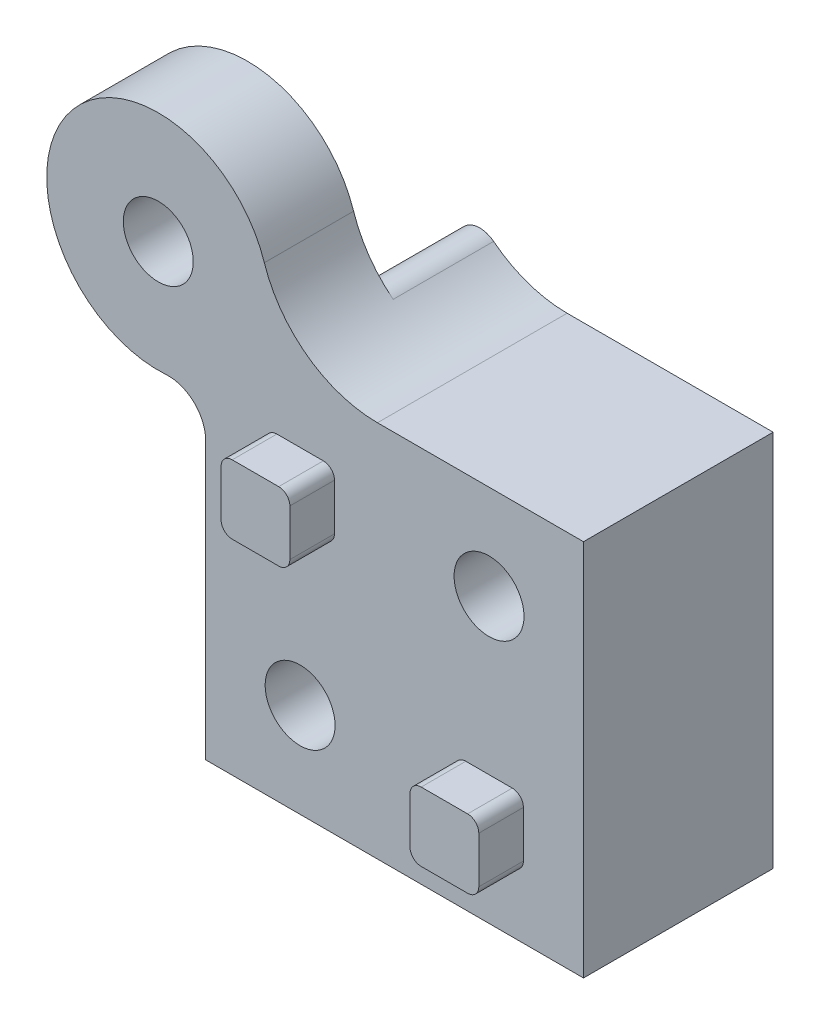
SolidWorks part; units mm, degrees
ref_plane "Front Plane" through (0, 0, 0) normal (0, 0, 1) x (1, 0, 0)
ref_plane "Top Plane" through (0, 0, 0) normal (0, 1, 0) x (1, 0, 0)
ref_plane "Right Plane" through (0, 0, 0) normal (1, 0, 0) x (0, 0, -1)
sketch "Sketch2" plane through (0, 0, 0) normal (0, 0, 1) x (1, 0, 0)
  line L0 (38.1, 165.1) -> (90.6036, 217.6036) construction
  line L1 (59.4614, 181.8386) -> (54.8386, 181.8386) construction
  line L2 (59.4614, 181.8386) -> (59.4614, 186.4614) construction
  line L3 (59.4614, 186.4614) -> (54.8386, 186.4614) construction
  line L4 (54.8386, 181.8386) -> (54.8386, 186.4614) construction
  line L5 (59.4614, 169.1386) -> (54.8386, 169.1386) construction
  line L6 (59.4614, 169.1386) -> (59.4614, 173.7614) construction
  line L7 (59.4614, 173.7614) -> (54.8386, 173.7614) construction
  line L8 (54.8386, 169.1386) -> (54.8386, 173.7614) construction
  line L9 (46.7614, 169.1386) -> (42.1386, 169.1386) construction
  line L10 (46.7614, 169.1386) -> (46.7614, 173.7614) construction
  line L11 (46.7614, 173.7614) -> (42.1386, 173.7614) construction
  line L12 (42.1386, 169.1386) -> (42.1386, 173.7614) construction
  line L13 (46.7614, 181.8386) -> (42.1386, 181.8386) construction
  line L14 (46.7614, 181.8386) -> (46.7614, 186.4614) construction
  line L15 (46.7614, 186.4614) -> (42.1386, 186.4614) construction
  line L16 (42.1386, 181.8386) -> (42.1386, 186.4614) construction
  line L17 (38.1, 165.1) -> (63.5, 165.1) construction
  line L18 (38.1, 165.1) -> (38.1, 190.5) construction
  line L19 (38.1, 190.5) -> (63.5, 190.5) construction
  line L20 (63.5, 165.1) -> (63.5, 190.5) construction
  line L21 (66.682, 205.8881) -> (66.682, 160.5985) construction
  line L22 (95.264, 165.1) -> (95.264, 190.5) construction
  line L23 (95.264, 165.1) -> (69.864, 165.1) construction
  line L24 (73.9026, 173.7614) -> (78.5254, 173.7614) construction
  line L25 (78.5254, 169.1386) -> (78.5254, 173.7614) construction
  line L26 (73.9026, 169.1386) -> (73.9026, 173.7614) construction
  line L27 (73.9026, 169.1386) -> (78.5254, 169.1386) construction
  line L28 (91.2254, 169.1386) -> (91.2254, 173.7614) construction
  line L29 (86.6026, 169.1386) -> (91.2254, 169.1386) construction
  line L30 (86.6026, 169.1386) -> (86.6026, 173.7614) construction
  line L31 (86.6026, 173.7614) -> (91.2254, 173.7614) construction
  line L32 (86.6026, 181.8386) -> (91.2254, 181.8386) construction
  line L33 (91.2254, 181.8386) -> (91.2254, 186.4614) construction
  line L34 (86.6026, 186.4614) -> (91.2254, 186.4614) construction
  line L35 (86.6026, 181.8386) -> (86.6026, 186.4614) construction
  line L36 (73.9026, 181.8386) -> (78.5254, 181.8386) construction
  line L37 (73.9026, 181.8386) -> (73.9026, 186.4614) construction
  line L38 (73.9026, 186.4614) -> (78.5254, 186.4614) construction
  line L39 (78.5254, 181.8386) -> (78.5254, 186.4614) construction
  line L40 (95.264, 190.5) -> (69.864, 190.5) construction
  line L41 (69.864, 165.1) -> (69.864, 190.5) construction
  circle A0 centre (66.682, 193.682) radius 2.35 construction
  circle A1 centre (66.682, 193.682) radius 7.5 construction
  dimension "D1" = 4.6228
  dimension "D6" = 4.7
  dimension "D7" = 4.5
  dimension "D10" = 15
  dimension "D2" = 4.0386
  dimension "D3" = 4.0386
  dimension "D4" = 45
  dimension "D5" = 25.4
  dimension "D8" = 8.0772
  dimension "D9" = 8.0772
sketch "Sketch3" plane through (0, 0, 0) normal (0, 0, 1) x (1, 0, 0)
  line L0 (78.5254, 186.4614) -> (73.9026, 186.4614)
  line L1 (73.9026, 186.4614) -> (73.9026, 181.8386)
  line L2 (73.9026, 181.8386) -> (78.5254, 181.8386)
  line L3 (78.5254, 181.8386) -> (78.5254, 186.4614)
  line L4 (86.6026, 173.7614) -> (86.6026, 169.1386)
  line L5 (86.6026, 169.1386) -> (91.2254, 169.1386)
  line L6 (91.2254, 169.1386) -> (91.2254, 173.7614)
  line L7 (91.2254, 173.7614) -> (86.6026, 173.7614)
  circle A0 centre (88.914, 184.15) radius 2.35
  circle A1 centre (76.214, 171.45) radius 2.35
extrude "Boss-Extrude1" add sketch "Sketch3" along normal blind 3
sketch "Sketch4" plane through (0, 0, 0) normal (0, 0, -1) x (-1, 0, 0)
  line L0 (-95.264, 190.5) -> (-69.864, 190.5)
  line L1 (-69.864, 190.5) -> (-69.864, 165.1)
  line L2 (-69.864, 165.1) -> (-95.264, 165.1)
  line L3 (-95.264, 165.1) -> (-95.264, 190.5)
  circle A0 centre (-66.682, 193.682) radius 2.35
  circle A1 centre (-66.682, 193.682) radius 7.5
  circle M1 centre (-88.914, 184.15) radius 2.35
extrude "Boss-Extrude2" add sketch "Sketch4" along normal blind 6 contours L1 A1 L0 A0 | L0 A1 L1 | A1 L0 L3 L2 L1 M1 | M1 region at (82.5337, 177.4748, 0) region at (68.2658, 200.7957, 0) region at (71.2059, 189.158, 0) region at (88.914, 184.15, 0)
sketch "Sketch6" plane through (0, 0, -6) normal (0, 0, -1) x (-1, 0, 0)
  line L0 (-69.864, 186.8904) -> (-69.864, 165.1) construction
  line L1 (-95.264, 190.5) -> (-73.4735, 190.5) construction
  line L2 (-73.7486, 190.5) -> (-95.264, 190.5)
  line L3 (-95.264, 190.5) -> (-95.264, 165.1)
  line L4 (-95.264, 165.1) -> (-69.864, 165.1)
  line L5 (-69.864, 165.1) -> (-69.864, 186.6153)
  arc A0 (-69.864, 186.6153) -> (-73.7486, 190.5) centre (-66.682, 193.682) cw
extrude "Boss-Extrude3" add sketch "Sketch6" along normal blind 6.75
sketch "Sketch7" plane through (0, 0, 3) normal (0, 0, 1) x (1, 0, 0)
  circle A0 centre (88.914, 184.15) radius 2.35
  circle A1 centre (76.214, 171.45) radius 2.35
extrude "Cut-Extrude2" cut sketch "Sketch7" against normal through all
fillet "Fillet1" radius 8 1 edges at (73.4735, 190.5, -3)
fillet "Fillet2" radius 2.5 1 edges at (69.864, 186.8904, -3)
fillet "Fillet3" radius 1.5 1 edges at (74.3617, 194.7234, -9.375)
fillet "Fillet4" radius 0.75 8 edges at (86.6026, 169.1386, 1.5) (91.2254, 169.1386, 1.5) (91.2254, 173.7614, 1.5) (86.6026, 173.7614, 1.5) (78.5254, 181.8386, 1.5) (73.9026, 181.8386, 1.5) (78.5254, 186.4614, 1.5) (73.9026, 186.4614, 1.5)
